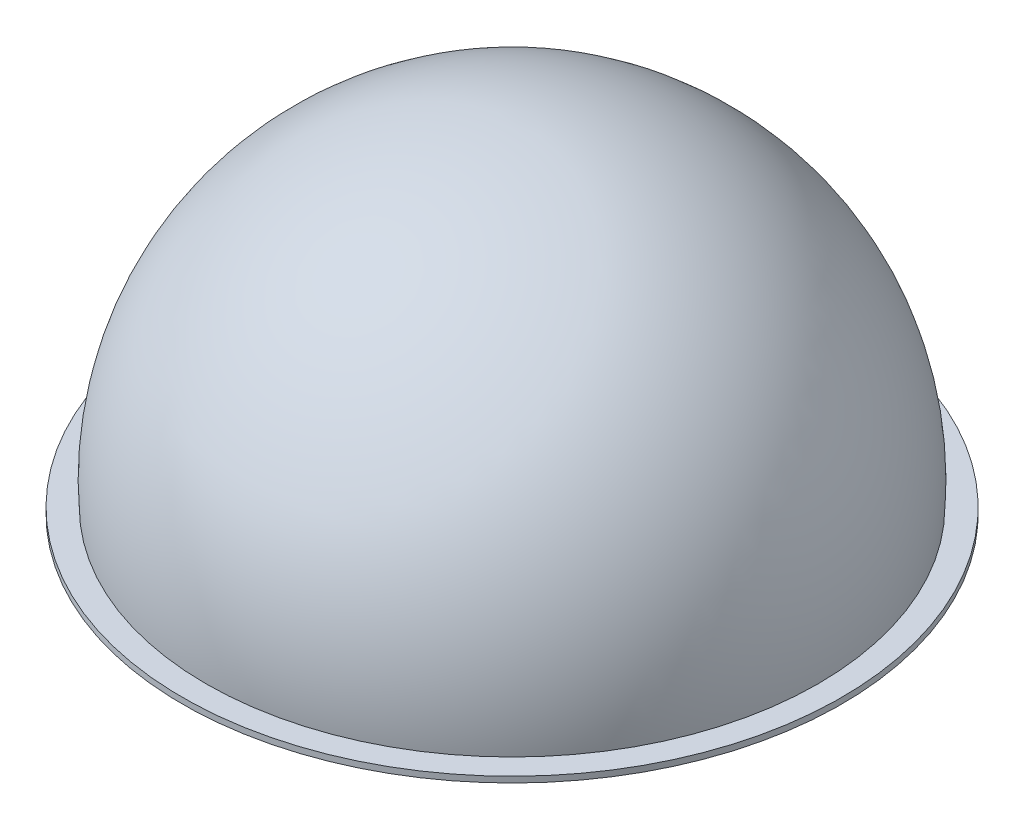
SolidWorks part; units mm, degrees
material "Acrylic (Medium-high impact)"
ref_plane "Front Plane" through (0, 0, 0) normal (0, 0, 1) x (1, 0, 0)
ref_plane "Top Plane" through (0, 0, 0) normal (0, 1, 0) x (1, 0, 0)
ref_plane "Right Plane" through (0, 0, 0) normal (1, 0, 0) x (0, 0, -1)
sketch "Sketch1" plane through (0, 0, 0) normal (0, 0, 1) x (1, 0, 0)
  line L0 (0, 0) -> (0, 177.8) construction
  line L1 (0, 0) -> (165.1, 0) construction
  line L2 (0, 177.8) -> (0, 0)
  line L3 (0, 0) -> (165.1, 0)
  arc A0 (0, 177.8) -> (165.1, 0) centre (0, 12.2464) cw
  dimension "D1" = 177.8
  dimension "D2" = 165.1
revolve "Revolve1" add sketch "Sketch1" angle 360 about L2
sketch "Sketch3" plane through (0, 0, 0) normal (0, -1, 0) x (1, 0, 0)
  circle A0 centre (0, 0) radius 177.8
  dimension "D1" = 355.6
extrude "Boss-Extrude1" add sketch "Sketch3" along normal blind 3.175
shell "Shell1" thickness 3.175 removed face at (0, -3.175, -177.8)
